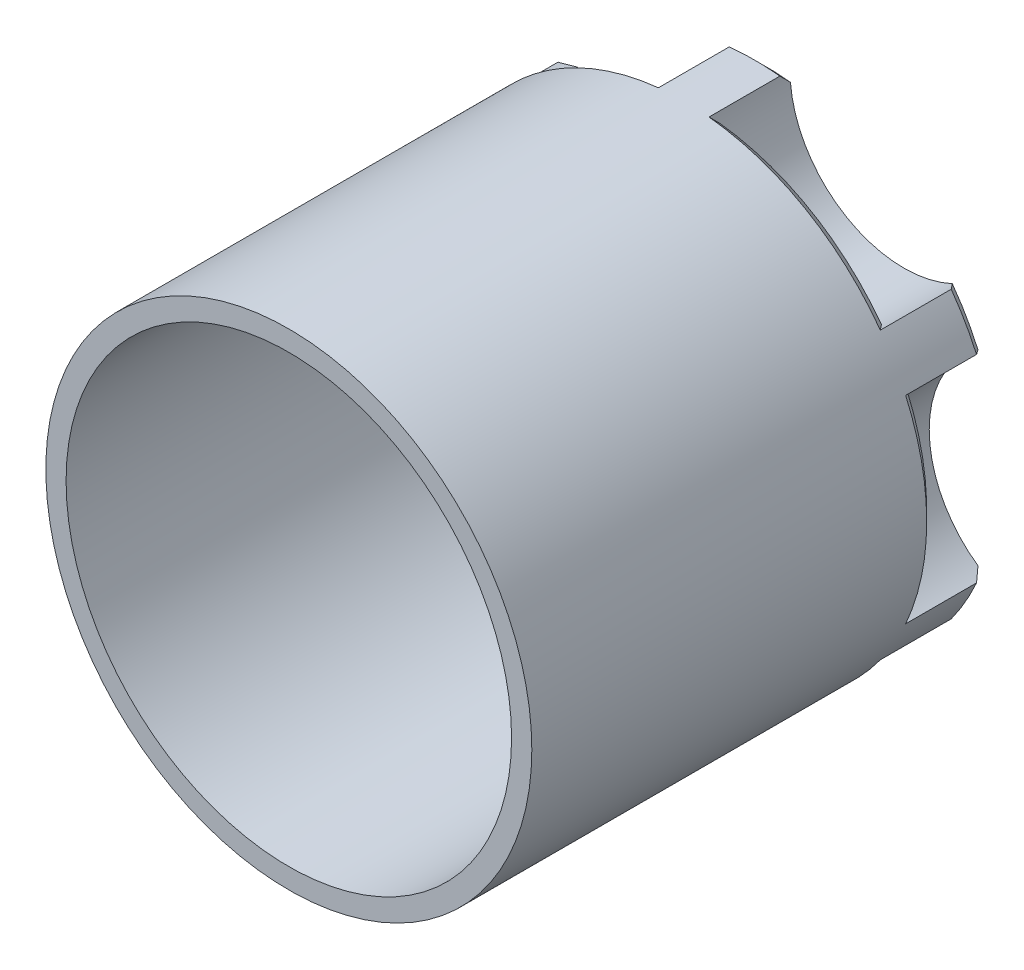
SolidWorks part; units mm, degrees
ref_plane "Front Plane" through (0, 0, 0) normal (0, 0, 1) x (1, 0, 0)
ref_plane "Top Plane" through (0, 0, 0) normal (0, 1, 0) x (1, 0, 0)
ref_plane "Right Plane" through (0, 0, 0) normal (1, 0, 0) x (0, 0, -1)
sketch "Sketch1" plane through (0, 0, 0) normal (0, 0, 1) x (1, 0, 0)
  line L0 (-1.4524, 0) -> (71.008, 0) construction
  line L1 (0, 0) -> (0, 72.303) construction
  circle A1 centre (0, 0) radius 24
  circle A2 centre (0, 0) radius 22
  arc A3 (21.9216, 9.7695) -> (21.9216, -9.7695) centre (27.5, 0) ccw
  arc A4 (19.358, 10.4532) -> (19.358, -10.4532) centre (27.5, 0) ccw
  circle A5 centre (27.5, 0) radius 13.25 construction
  circle A6 centre (27.5, 0) radius 11.25 construction
  arc A7 (18.7317, -11.5379) -> (0.6262, -21.9911) centre (13.75, -23.8157) ccw
  arc A8 (19.4215, -14.0999) -> (2.5001, -23.8694) centre (13.75, -23.8157) ccw
  arc A9 (-0.6262, -21.9911) -> (-18.7317, -11.5379) centre (-13.75, -23.8157) ccw
  arc A10 (-2.5001, -23.8694) -> (-19.4215, -14.0999) centre (-13.75, -23.8157) ccw
  arc A11 (-19.358, -10.4532) -> (-19.358, 10.4532) centre (-27.5, 0) ccw
  arc A12 (-21.9216, -9.7695) -> (-21.9216, 9.7695) centre (-27.5, 0) ccw
  arc A13 (-18.7317, 11.5379) -> (-0.6262, 21.9911) centre (-13.75, 23.8157) ccw
  arc A14 (-19.4215, 14.0999) -> (-2.5001, 23.8694) centre (-13.75, 23.8157) ccw
  arc A15 (0.6262, 21.9911) -> (18.7317, 11.5379) centre (13.75, 23.8157) ccw
  arc A16 (2.5001, 23.8694) -> (19.4215, 14.0999) centre (13.75, 23.8157) ccw
  arc A17 (16.724, 17.2136) -> (6.5455, 23.0902) centre (0, 0) ccw construction
  point P50 (0, 0)
  dimension "D2" = 22.5
  dimension "D6" = 0
  dimension "D1" = 2
  dimension "D3" = 27.5
  dimension "D4" = 2
  dimension "D5" = 6
extrude "Boss-Extrude1" add sketch "Sketch1" along normal blind 3 and the other way blind 37 contours A1 A14 A2 | A1 A16 A2 | A16 A1 A14 A2 | A16 A2 A3 A1 | A1 A3 A2 | A1 A8 A2 | A8 A1 A3 A2 | A10 A1 A8 A2 | A2 A10 A1 | A12 A1 A10 A2 | A2 A12 A1 | A14 A1 A12 A2 region at (22.3744, 0, 0) region at (19.8673, 11.4704, 0) region at (19.8673, -11.4704, 0) region at (11.1872, 19.3768, 0) region at (11.1872, -19.3768, 0) region at (0, 22.9408, 0) region at (0, -22.9408, 0) region at (-11.1872, 19.3768, 0) region at (-11.1872, -19.3768, 0) region at (-19.8673, 11.4704, 0) region at (-19.8673, -11.4704, 0) region at (-22.3744, 0, 0)
extrude "Boss-Extrude2" add sketch "Sketch1<5>" along normal blind 2 from surface contours A2 A16 | A2 A14 | A2 A12 | A2 A10 | A2 A8 | A2 A3 | A14 A2 A13 | A16 A1 A14 A2 | A14 A1 A12 A2 | A12 A2 A11 | A12 A1 A10 A2 | A10 A2 A9 | A10 A1 A8 A2 | A8 A2 A7 | A8 A1 A3 A2 | A2 A4 A3 | A16 A2 A3 A1 | A16 A2 A15 region at (19.8673, 11.4704, 0) region at (19.8673, -11.4704, 0) region at (16.0325, 0, 0) region at (19.3155, 0, 0) region at (0, 22.9408, 0) region at (9.6577, 16.7277, 0) region at (17.9956, 12.2795, 0) region at (0, -22.9408, 0) region at (8.018, -13.8875, 0) region at (9.6577, -16.7277, 0) region at (-19.8673, 11.4704, 0) region at (-9.6577, 16.7277, 0) region at (-1.6366, 21.7244, 0) region at (-19.8673, -11.4704, 0) region at (-8.018, -13.8875, 0) region at (-9.6577, -16.7277, 0) region at (-19.3155, 0, 0) region at (-19.629, 9.4434, 0) starting at face at (24, 0, -37)
sketch "Sketch1<5>" plane through (0, 0, 0) normal (0, 0, 1) x (1, 0, 0) same geometry as "Sketch1"
extrude "Boss-Extrude4" add sketch "Sketch1<7>" against normal blind 5 from surface contours A14 A2 A13 | A14 A1 A12 A2 | A12 A2 A11 | A12 A1 A10 A2 | A10 A2 A9 | A10 A1 A8 A2 | A8 A2 A7 | A8 A1 A3 A2 | A2 A4 A3 | A16 A2 A3 A1 | A16 A2 A15 | A16 A1 A14 A2 region at (19.8673, 11.4704, 0) region at (19.8673, -11.4704, 0) region at (16.0325, 0, 0) region at (0, 22.9408, 0) region at (17.9956, 12.2795, 0) region at (0, -22.9408, 0) region at (8.018, -13.8875, 0) region at (-19.8673, 11.4704, 0) region at (-1.6366, 21.7244, 0) region at (-19.8673, -11.4704, 0) region at (-8.018, -13.8875, 0) region at (-19.629, 9.4434, 0) starting at face at (0, 0, -37)
sketch "Sketch1<7>" plane through (0, 0, 0) normal (0, 0, 1) x (1, 0, 0) same geometry as "Sketch1"
extrude "Boss-Extrude5" add sketch "Sketch1<8>" against normal blind 2 from surface contours A14 A2 A13 | A16 A1 A14 A2 | A16 A2 A15 | A15 A2 A13 A11 A9 A7 A4 | A2 A4 A3 | A16 A2 A3 A1 | A8 A1 A3 A2 | A8 A2 A7 | A10 A1 A8 A2 | A10 A2 A9 | A12 A1 A10 A2 | A12 A2 A11 | A14 A1 A12 A2 region at (19.8673, 11.4704, 0) region at (19.8673, -11.4704, 0) region at (16.0325, 0, 0) region at (0, 22.9408, 0) region at (17.9956, 12.2795, 0) region at (0, 0, 0) region at (0, -22.9408, 0) region at (8.018, -13.8875, 0) region at (-19.8673, 11.4704, 0) region at (-1.6366, 21.7244, 0) region at (-19.8673, -11.4704, 0) region at (-8.018, -13.8875, 0) region at (-19.629, 9.4434, 0) starting at face at (0, 0, -42)
sketch "Sketch1<8>" plane through (0, 0, 0) normal (0, 0, 1) x (1, 0, 0) same geometry as "Sketch1"
chamfer "Chamfer1" distance 1 angle 45 12 edges at (-20.7846, 12, -44) (-20.7846, -12, -44) (0, -24, -44) (20.7846, -12, -44) (20.7846, 12, -44) (0, 24, -44) (24, 0, -37) (12, -20.7846, -37) (-12, -20.7846, -37) (-24, 0, -37) (-12, 20.7846, -37) (12, 20.7846, -37)
